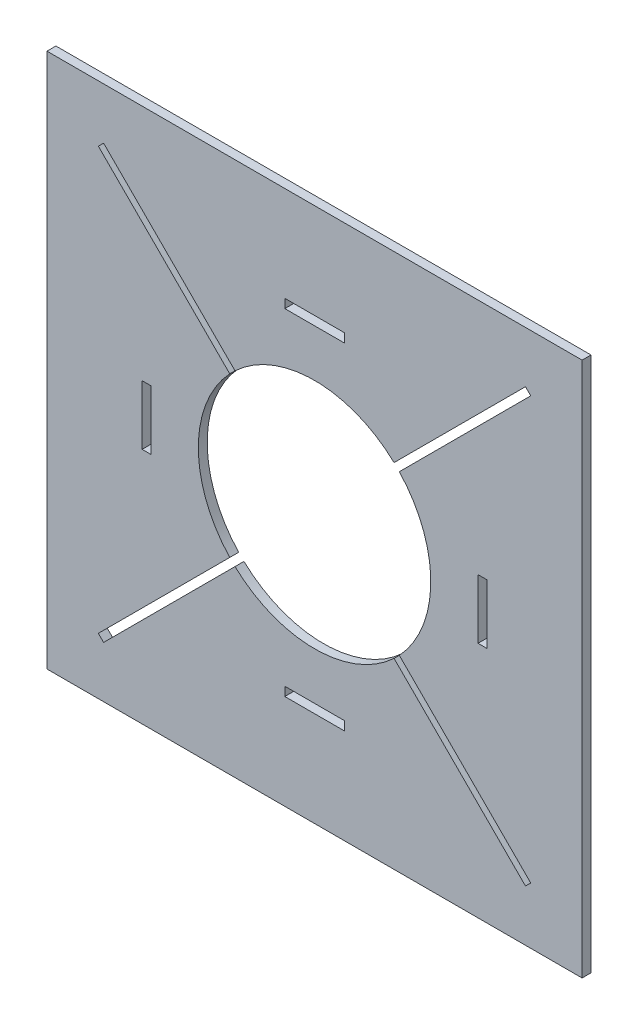
SolidWorks part; units mm, degrees
material "Pine"
ref_plane "Front Plane" through (0, 0, 0) normal (0, 0, 1) x (1, 0, 0)
ref_plane "Top Plane" through (0, 0, 0) normal (0, 1, 0) x (1, 0, 0)
ref_plane "Right Plane" through (0, 0, 0) normal (1, 0, 0) x (0, 0, -1)
sketch "Sketch1" plane through (0, 0, 0) normal (0, 0, 1) x (1, 0, 0)
  line L1 (-180, -180) -> (180, -180)
  line L2 (-180, -180) -> (-180, 180)
  line L3 (-180, 180) -> (180, 180)
  line L4 (180, -180) -> (180, 180)
  point P5 (0, 180)
  point P6 (180, 0)
  dimension "D1" = 360
extrude "Boss-Extrude1" add sketch "Sketch1" along normal blind 6
sketch "Sketch2" plane through (0, 0, 6) normal (0, 0, 1) x (1, 0, 0)
  line L0 (180, 180) -> (-180, 180) construction
  line L1 (-180, 180) -> (-180, -180) construction
  circle A0 centre (0, 0) radius 78.2
  point P2 (0, 0)
  point P5 (0, 180)
  point P8 (-180, 0)
  dimension "D1" = 156.4
extrude "Cut-Extrude1" cut sketch "Sketch2" against normal through all
sketch "Sketch3" plane through (0, 0, 6) normal (0, 0, 1) x (1, 0, 0)
  line L0 (0, 0) -> (-143.6841, 143.6841) construction
  line L1 (0, 0) -> (0, 78.2) construction
  line L2 (-57.0353, 53.4997) -> (-145.4519, 141.9163)
  line L3 (-145.4519, 141.9163) -> (-141.9163, 145.4519)
  line L4 (-141.9163, 145.4519) -> (-53.4997, 57.0353)
  circle A0 centre (0, 0) radius 78.2 construction
  arc A1 (-53.4997, 57.0353) -> (-57.0353, 53.4997) centre (0, 0) ccw
  dimension "D1" = 45
  dimension "D2" = 203.2
  dimension "D3" = 5
extrude "Cut-Extrude2" cut sketch "Sketch3" against normal through all
ref_axis "Axis1" through (0, 0, -0.3) along (0, 0, 1)
pattern_circular "CirPattern1" count 4 over 360 about axis through (0, 0, -0.3) along (0, 0, 1) of "Cut-Extrude2"
sketch "Sketch4" plane through (0, 0, 6) normal (0, 0, 1) x (1, 0, 0)
  line L1 (-20, 116) -> (20, 116)
  line L2 (-20, 116) -> (-20, 110)
  line L3 (-20, 110) -> (20, 110)
  line L4 (20, 116) -> (20, 110)
  point P4 (0, 110)
  dimension "D1" = 6
  dimension "D2" = 40
  dimension "D3" = 110
extrude "Cut-Extrude3" cut sketch "Sketch4" against normal through all contours L1 L4 L3 L2
pattern_circular "CirPattern2" count 4 over 360 about axis through (0, 0, -0.3) along (0, 0, 1) of "Cut-Extrude3"
